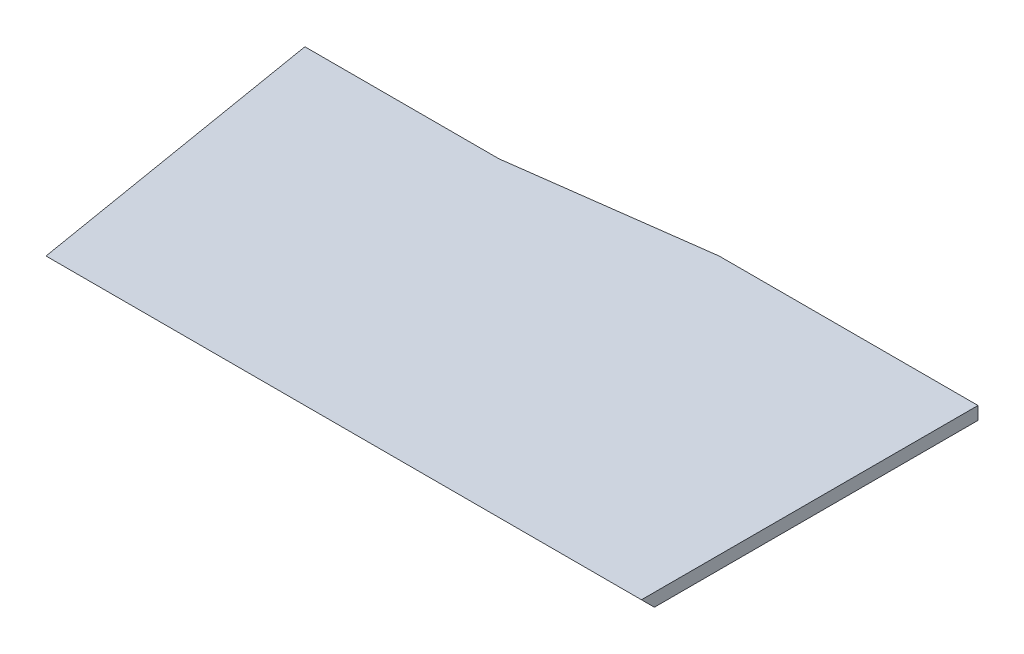
SolidWorks part; units mm, degrees
material "Titanium Ti-8Al-1Mo-1V"
ref_plane "Front Plane" through (0, 0, 0) normal (0, 0, 1) x (1, 0, 0)
ref_plane "Top Plane" through (0, 0, 0) normal (0, 1, 0) x (1, 0, 0)
ref_plane "Right Plane" through (0, 0, 0) normal (1, 0, 0) x (0, 0, -1)
sketch "Sketch1" plane through (0, 0, 0) normal (0, 1, 0) x (1, 0, 0)
  line L6 (0, -50) -> (0, 0)
  line L7 (-92, -50) -> (0, -50)
  line L8 (-100, -2) -> (-92, -50)
  line L9 (-70, -2) -> (-100, -2)
  line L10 (-40, 2) -> (-70, -2)
  line L11 (0, 2) -> (-40, 2)
  line L12 (0, 0) -> (0, 2)
  dimension "D1" = 48
extrude "Boss-Extrude1" add sketch "Sketch1" along normal blind 2
chamfer "Chamfer1" distance 2 angle 45 1 edges at (-46, 0, 50)
